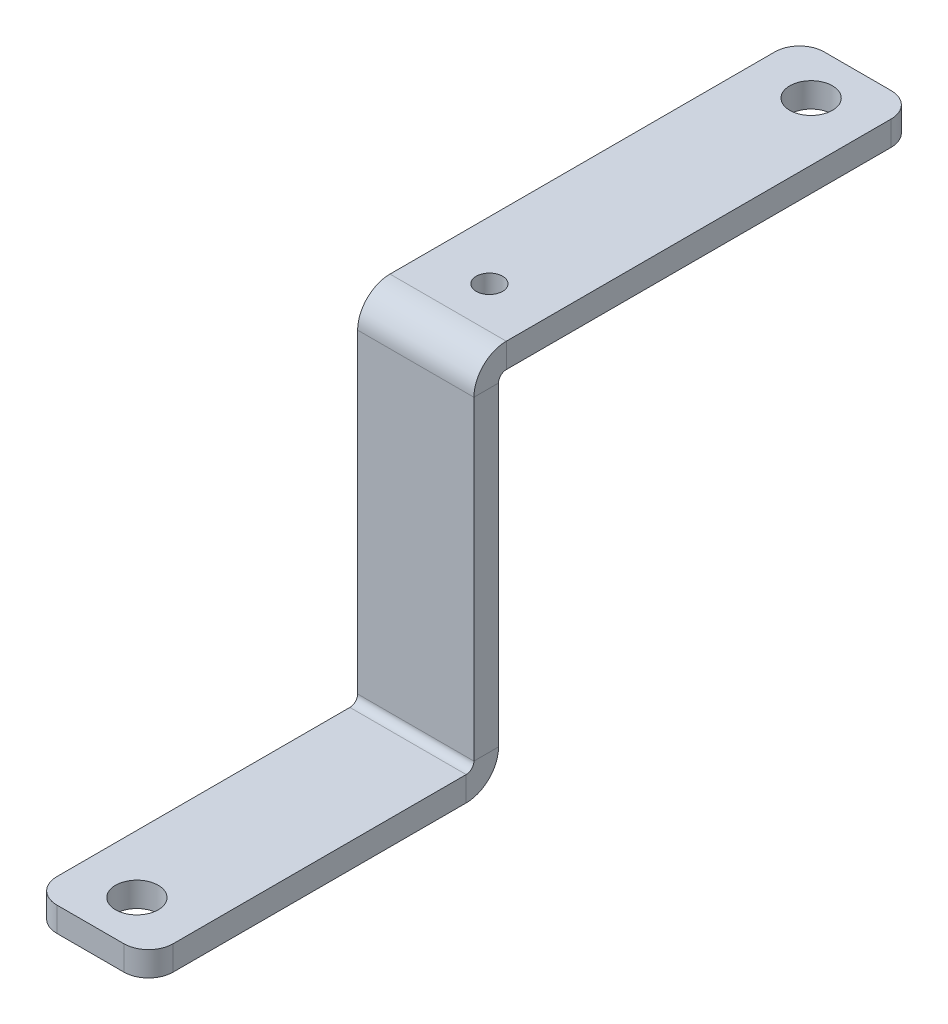
SolidWorks part; units mm, degrees
note: The reader was unsure of these and kept them because the rebuilt part matched: thickness of "Base-Flange1", "Edge-Flange1", "Edge-Flange2", "Sheet-Metal1", "Sheet-Metal2", "Sheet-Metal3", "Sheet-Metal4", "Sheet-Metal5", "Sheet-Metal6"; flange length of "Edge-Flange1", "Edge-Flange2".
material "3003-H14"
ref_plane "Front Plane" through (0, 0, 0) normal (0, 0, 1) x (1, 0, 0)
ref_plane "Top Plane" through (0, 0, 0) normal (0, 1, 0) x (1, 0, 0)
ref_plane "Right Plane" through (0, 0, 0) normal (1, 0, 0) x (0, 0, -1)
sketch "Sketch1" plane through (0, 0, 0) normal (0, 1, 0) x (1, 0, 0)
  line L5 (-7.5, -22.575) -> (7.5, -22.575)
  line L6 (-7.5, -22.575) -> (-7.5, 22.575)
  line L7 (-7.5, 22.575) -> (7.5, 22.575)
  line L8 (7.5, -22.575) -> (7.5, 22.575)
  line L9 (-7.5, -22.575) -> (7.5, 22.575) construction
  line L10 (-7.5, 22.575) -> (7.5, -22.575) construction
  point P0 (0, 0)
  dimension "D1" = 45.15
  dimension "D2" = 15
base flange "Base-Flange1" sketch "Sketch1" thickness 3.175 reverse thickness direction no parameters "D1"=0.7366
edge flange "Edge-Flange1" sketch "Sketch8" flange angle 90 flange length 49 flange position material inside bend radius 1 thickness 3.175 relief rectangular parameters "D6"=10
sketch "Sketch8" plane through (0, 0, -22.575) normal (0, 0, -1) x (-1, 0, 0)
  line L0 (-7.5, 0) -> (7.5, 0) construction
  line L1 (-7.5, 0) -> (7.5, 0)
  line L2 (-7.5, 0) -> (-7.5, 45.825)
  line L3 (-7.5, 45.825) -> (7.5, 45.825)
  line L4 (7.5, 45.825) -> (7.5, 0)
bend "EdgeBend1" bend radius 1 bend angle 90 parameters "D5"=1
edge flange "Edge-Flange2" sketch "Sketch11" flange angle 90 flange length 57 flange position material inside bend radius 1 thickness 3.175 relief rectangular parameters "D6"=10
sketch "Sketch11" plane through (0, 45.825, -22.575) normal (0, 1, 0) x (1, 0, 0)
  line L0 (-7.5, 0) -> (7.5, 0) construction
  line L1 (-7.5, 0) -> (7.5, 0)
  line L2 (-7.5, 0) -> (-7.5, 53.825)
  line L3 (-7.5, 53.825) -> (7.5, 53.825)
  line L4 (7.5, 53.825) -> (7.5, 0)
bend "EdgeBend2" bend radius 1 bend angle 90 parameters "D5"=2
hole_wizard "M5 Clearance Hole2" positions "Sketch12" profile "Sketch13" hole size "M5" standard "ANSI Metric" end condition through all
sketch "Sketch12" plane through (0, 0, 0) normal (0, 1, 0) x (1, 0, 0)
  line L0 (-7.5, -22.575) -> (7.5, -22.575) construction
  point P0 (0, -16.575)
  dimension "D1" = 6
sketch "Sketch13" plane through (0, 0, 16.575) normal (1, 0, 0) x (0, 0, 1)
  line L0 (0, 0) -> (0, 3.175)
  line L1 (0, 3.175) -> (2.75, 3.175)
  line L2 (2.75, 3.175) -> (2.75, 0)
  line L5 (2.75, 0) -> (0, 0)
  line L11 (0, -6.35) -> (0, 107.95) construction
  dimension "Thru Hole Dia." = 5.5
  dimension "Thru Hole Depth" = 3.175
hole_wizard "M5 Clearance Hole1" positions "Sketch14" profile "Sketch15" hole size "M5" standard "ANSI Metric" end condition through all
sketch "Sketch14" plane through (0, 45.825, 0) normal (0, 1, 0) x (1, 0, 0)
  line L0 (7.5, 76.4) -> (-7.5, 76.4) construction
  line L1 (-7.5, 76.4) -> (-7.5, 23.575) construction
  point P0 (0, 70.4)
  dimension "D1" = 6
  dimension "D2" = 7.5
sketch "Sketch15" plane through (0, 45.825, -70.4) normal (1, 0, 0) x (0, 0, 1)
  line L0 (0, 0) -> (0, 49)
  line L1 (0, 49) -> (2.75, 49)
  line L2 (2.75, 49) -> (2.75, 0)
  line L5 (2.75, 0) -> (0, 0)
  line L11 (0, -6.35) -> (0, 107.95) construction
  dimension "Thru Hole Dia." = 5.5
  dimension "Thru Hole Depth" = 49
hole_wizard "M3 Clearance Hole1" positions "Sketch16" profile "Sketch17" hole size "M3" standard "ANSI Metric" end condition through all
sketch "Sketch16" plane through (0, 45.825, 0) normal (0, 1, 0) x (1, 0, 0)
  line L0 (7.5, 19.4) -> (-7.5, 19.4) construction
  line L1 (-7.5, 76.4) -> (-7.5, 23.575) construction
  point P0 (0, 28.9)
  dimension "D1" = 9.5
  dimension "D2" = 7.5
sketch "Sketch17" plane through (0, 45.825, -28.9) normal (1, 0, 0) x (0, 0, 1)
  line L0 (0, 0) -> (0, 49)
  line L1 (0, 49) -> (1.7, 49)
  line L2 (1.7, 49) -> (1.7, 0)
  line L5 (1.7, 0) -> (0, 0)
  line L11 (0, -6.35) -> (0, 107.95) construction
  dimension "Thru Hole Dia." = 3.4
  dimension "Thru Hole Depth" = 49
fillet "Fillet1" radius 3.175 4 edges at (-7.5, 44.2375, -76.4) (7.5, 44.2375, -76.4) (-7.5, -1.5875, 22.575) (7.5, -1.5875, 22.575)
sketch "Bend-Lines1" [suppressed] plane through (0, 0, 0) normal (0, 1, 0) x (1, 0, 0)
sketch "Bounding-Box1" [suppressed] plane through (0, 0, 0) normal (0, 1, 0) x (1, 0, 0)
sheet metal parameters "Sheet-Metal1" thickness 3.175 parameters "D1"=0.7366
flat pattern "Flat-Pattern1" [suppressed]
sketch "Bend-Lines2" plane through (0, 0, 0) normal (0, 1, 0) x (1, 0, 0)
sketch3d "Bounding-Box2" [suppressed]
  line L0 (-2.5, -12.5, 0) -> (-2.5, 12.5, 0) construction
  line L1 (2.5, -12.5, 0) -> (2.5, 12.5, 0) construction
  line L2 (-2.5, -12.5, 0) -> (2.5, -12.5, 0) construction
  line L3 (-2.5, 12.5, 0) -> (2.5, 12.5, 0) construction
sheet metal parameters "Sheet-Metal2" thickness 3.175 parameters "D1"=0.7366, "D7"=3.18
flat pattern "Flat-Pattern1"
sketch "Bend-Lines2" plane through (0, 0, 0) normal (0, 1, 0) x (1, 0, 0)
  line L0 (2.5, 10.4107) -> (-2.5, 10.4107) construction
  line L1 (2.5, 10.4107) -> (-2.5, 10.4107) construction
sketch3d "Bounding-Box2" [suppressed]
  line L0 (-2.5, -12.5, 0) -> (-2.5, 33.3214, 0) construction
  line L1 (2.5, -12.5, 0) -> (2.5, 33.3214, 0) construction
  line L2 (-2.5, -12.5, 0) -> (2.5, -12.5, 0) construction
  line L3 (-2.5, 33.3214, 0) -> (2.5, 33.3214, 0) construction
bend of the flat pattern "Flatten-<EdgeBend1>1"
sheet metal parameters "Sheet-Metal3" thickness 3.175 parameters "D1"=0.7366, "D7"=3.18
flat pattern "Flat-Pattern1"
sketch "Bend-Lines2" plane through (0, 0, 0) normal (0, 1, 0) x (1, 0, 0)
  line L0 (7.5, 10.4107) -> (-7.5, 10.4107) construction
  line L1 (7.5, 10.4107) -> (-7.5, 10.4107) construction
  line L2 (7.5, 31.2321) -> (-7.5, 31.2321) construction
  line L3 (7.5, 31.2321) -> (-7.5, 31.2321) construction
sketch3d "Bounding-Box2" [suppressed]
  line L0 (-7.5, -12.5, 0) -> (-7.5, 64.1428, 0) construction
  line L1 (7.5, -12.5, 0) -> (7.5, 64.1428, 0) construction
  line L2 (-7.5, -12.5, 0) -> (7.5, -12.5, 0) construction
  line L3 (-7.5, 64.1428, 0) -> (7.5, 64.1428, 0) construction
bend of the flat pattern "Flatten-<EdgeBend1>1"
bend of the flat pattern "Flatten-<EdgeBend2>1"
sheet metal parameters "Sheet-Metal4" thickness 3.175 parameters "D1"=0.7366, "D7"=3.18
flat pattern "Flat-Pattern1"
sketch "Bend-Lines2" plane through (0, 0, 0) normal (0, 1, 0) x (1, 0, 0)
  line L0 (7.5, 10.4107) -> (-7.5, 10.4107) construction
  line L1 (7.5, 10.4107) -> (-7.5, 10.4107) construction
  line L2 (7.5, 31.2321) -> (-7.5, 31.2321) construction
  line L3 (7.5, 31.2321) -> (-7.5, 31.2321) construction
sketch3d "Bounding-Box2" [suppressed]
  line L0 (-7.5, -12.5, 0) -> (-7.5, 64.1428, 0) construction
  line L1 (7.5, -12.5, 0) -> (7.5, 64.1428, 0) construction
  line L2 (-7.5, -12.5, 0) -> (7.5, -12.5, 0) construction
  line L3 (-7.5, 64.1428, 0) -> (7.5, 64.1428, 0) construction
bend of the flat pattern "Flatten-<EdgeBend1>1"
bend of the flat pattern "Flatten-<EdgeBend2>1"
sheet metal parameters "Sheet-Metal5" thickness 3.175 parameters "D1"=0.7366, "D7"=3.18
flat pattern "Flat-Pattern1"
sketch "Bend-Lines2" plane through (0, 0, 0) normal (0, 1, 0) x (1, 0, 0)
  line L0 (7.5, 10.4107) -> (-7.5, 10.4107) construction
  line L1 (7.5, 10.4107) -> (-7.5, 10.4107) construction
  line L2 (7.5, 31.2321) -> (-7.5, 31.2321) construction
  line L3 (7.5, 31.2321) -> (-7.5, 31.2321) construction
sketch3d "Bounding-Box2" [suppressed]
  line L0 (-7.5, -12.5, 0) -> (-7.5, 64.1428, 0) construction
  line L1 (7.5, -12.5, 0) -> (7.5, 64.1428, 0) construction
  line L2 (-7.5, -12.5, 0) -> (7.5, -12.5, 0) construction
  line L3 (-7.5, 64.1428, 0) -> (7.5, 64.1428, 0) construction
bend of the flat pattern "Flatten-<EdgeBend1>1"
bend of the flat pattern "Flatten-<EdgeBend2>1"
sheet metal parameters "Sheet-Metal6" thickness 3.175 parameters "D1"=0.7366, "D7"=3.18
flat pattern "Flat-Pattern1"
sketch "Bend-Lines2" plane through (0, 0, 0) normal (0, 1, 0) x (1, 0, 0)
  line L0 (7.5, 20.4322) -> (-7.5, 20.4322) construction
  line L1 (7.5, 20.4322) -> (-7.5, 20.4322) construction
  line L2 (7.5, 65.1467) -> (-7.5, 65.1467) construction
  line L3 (7.5, 65.1467) -> (-7.5, 65.1467) construction
sketch3d "Bounding-Box2" [suppressed]
  line L0 (-7.5, -22.575, 0) -> (-7.5, 120.0039, 0) construction
  line L1 (7.5, -22.575, 0) -> (7.5, 120.0039, 0) construction
  line L2 (-7.5, -22.575, 0) -> (7.5, -22.575, 0) construction
  line L3 (-7.5, 120.0039, 0) -> (7.5, 120.0039, 0) construction
bend of the flat pattern "Flatten-<EdgeBend1>1"
bend of the flat pattern "Flatten-<EdgeBend2>1"
